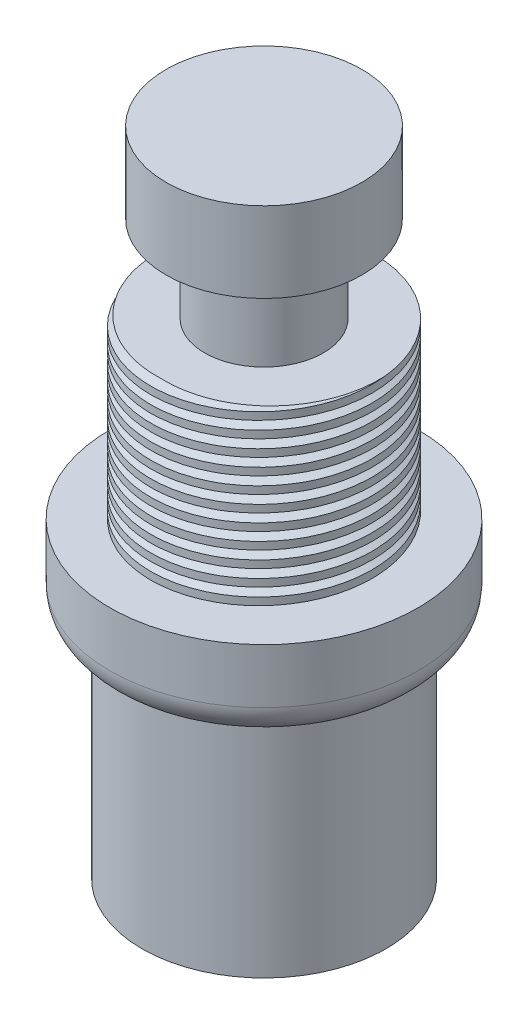
SolidWorks part; units mm, degrees
ref_plane "Front Plane" through (0, 0, 0) normal (0, 0, 1) x (1, 0, 0)
ref_plane "Top Plane" through (0, 0, 0) normal (0, 1, 0) x (1, 0, 0)
ref_plane "Right Plane" through (0, 0, 0) normal (1, 0, 0) x (0, 0, -1)
sketch "Sketch1" plane through (0, 0, 0) normal (0, 1, 0) x (1, 0, 0)
  circle A0 centre (0, 0) radius 3.8
  dimension "D1" = 7.6
extrude "Boss-Extrude1" add sketch "Sketch1" along normal blind 7
sketch "Sketch2" plane through (0, 7, 0) normal (0, 1, 0) x (1, 0, 0)
  circle A0 centre (0, 0) radius 4.8
  dimension "D1" = 9.6
extrude "Boss-Extrude2" add sketch "Sketch2" along normal blind 2.7
sketch "Sketch3" plane through (0, 9.7, 0) normal (0, 1, 0) x (1, 0, 0)
  circle A0 centre (0, 0) radius 3.45
  dimension "D1" = 6.9
extrude "Boss-Extrude3" add sketch "Sketch3" along normal blind 5.4
sketch "Sketch5" plane through (0, 15.1, 0) normal (0, 1, 0) x (1, 0, 0)
  circle A0 centre (0, 0) radius 3.45 construction
  circle A1 centre (0, 0) radius 3.45
curve "Helix/Spiral1" pitch 0.5 height 5.4 radius 3.45 centre (0, 15.1, 0) axis (0, -1, 0) start towards (0, 0, 1)
sketch "Sketch6" plane through (0, 0, 0) normal (1, 0, 0) x (0, 0, -1)
  line L1 (-3.2191, 15.1) -> (-3.5655, 15.3)
  line L2 (-3.5655, 15.3) -> (-3.5655, 14.9)
  line L3 (-3.5655, 14.9) -> (-3.2191, 15.1)
  circle A0 centre (-3.45, 15.1) radius 0.1155 construction
  dimension "D1" = 0.4
sweep "Cut-Sweep1" cut profiles "Sketch6" path "Helix/Spiral1" align with end faces yes
sketch "Sketch7" plane through (0, 15.1, 0) normal (0, 1, 0) x (1, 0, 0)
  circle A0 centre (0, 0) radius 1.85
  dimension "D1" = 3.7
extrude "Boss-Extrude4" add sketch "Sketch7" along normal blind 2.7
sketch "Sketch8" plane through (0, 17.8, 0) normal (0, 1, 0) x (1, 0, 0)
  circle A0 centre (0, 0) radius 3.05
  dimension "D1" = 6.1
extrude "Boss-Extrude5" add sketch "Sketch8" along normal blind 2.5
fillet "Fillet1" radius 1 1 edges at (0, 7, 4.8)
